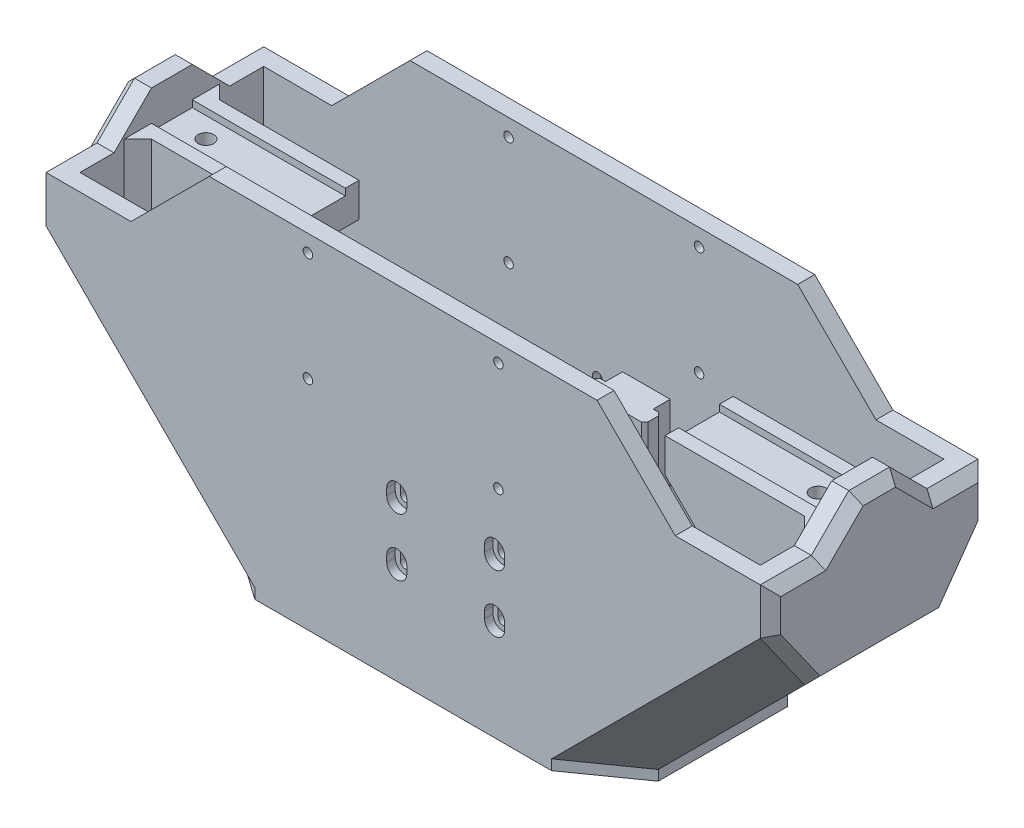
SolidWorks part; units mm, degrees
ref_plane "Front Plane" through (0, 0, 0) normal (0, 0, 1) x (1, 0, 0)
ref_plane "Top Plane" through (0, 0, 0) normal (0, 1, 0) x (1, 0, 0)
ref_plane "Right Plane" through (0, 0, 0) normal (1, 0, 0) x (0, 0, -1)
sketch "Sketch1" plane through (0, 0, 0) normal (0, 1, 0) x (1, 0, 0)
  line L1 (-100, -27) -> (100, -27)
  line L2 (-100, -27) -> (-100, 27)
  line L3 (-100, 27) -> (100, 27)
  line L4 (100, -27) -> (100, 27)
  line L5 (-100, -27) -> (100, 27) construction
  line L6 (-100, 27) -> (100, -27) construction
  point P0 (0, 0)
  dimension "D1" = 200
  dimension "D2" = 54
extrude "Boss-Extrude1" add sketch "Sketch1" along normal blind 70
shell "Shell1" thickness 5 removed face at (0, 70, 0) outward yes
sketch "Sketch2" plane through (105, 0, 0) normal (1, 0, 0) x (0, 0, -1)
  line L0 (-17, 70) -> (-6, 81)
  line L1 (-32, 70) -> (32, 70) construction
  line L2 (-6, 81) -> (6, 81)
  line L3 (6, 81) -> (17, 70)
  line L4 (17, 70) -> (-17, 70)
  line L5 (0, 81) -> (0, 75) construction
  dimension "D1" = 11
  dimension "D2" = 45
  dimension "D3" = 45
  dimension "D4" = 12
extrude "Boss-Extrude2" add sketch "Sketch2" against normal blind 5
sketch "Sketch4" plane through (0, 0, -32) normal (0, 0, -1) x (-1, 0, 0)
  line L0 (-80, 70) -> (-57, 93)
  line L1 (-105, 70) -> (105, 70) construction
  line L2 (-57, 93) -> (57, 93)
  line L3 (57, 93) -> (80, 70)
  line L4 (80, 70) -> (-80, 70)
  line L5 (0, 93) -> (0, 70) construction
  line L6 (-105, 70) -> (-105, -5) construction
  dimension "D1" = 23
  dimension "D2" = 25
  dimension "D3" = 45
extrude "Boss-Extrude3" add sketch "Sketch4" against normal blind 5
sketch "Sketch3" plane through (0, 0, -32) normal (0, 0, -1) x (-1, 0, 0)
  line L1 (-28, 56) -> (28, 56) construction
  line L2 (-28, 56) -> (-28, 88) construction
  line L3 (-28, 88) -> (28, 88) construction
  line L4 (28, 56) -> (28, 88) construction
  line L5 (-28, 56) -> (28, 88) construction
  line L6 (-28, 88) -> (28, 56) construction
  line L7 (57, 93) -> (-57, 93) construction
  circle A0 centre (-28, 88) radius 1.4
  circle A1 centre (-28, 56) radius 1.4
  circle A2 centre (28, 88) radius 1.4
  circle A3 centre (28, 56) radius 1.4
  point P0 (0, 72)
  dimension "D1" = 2.8
  dimension "D2" = 56
  dimension "D3" = 32
  dimension "D4" = 5
extrude "Cut-Extrude1" cut sketch "Sketch3" against normal blind 6
mirror "Mirror4" about plane through (0, 0, 0) normal (0, 0, 1) of "Boss-Extrude3", "Cut-Extrude1"
mirror "Mirror5" about plane through (0, 0, 0) normal (1, 0, 0) of "Boss-Extrude2"
sketch "Sketch5" plane through (0, 0, 0) normal (0, 0, 1) x (1, 0, 0)
  line L0 (-100, 70) -> (-55, 70)
  line L1 (-55, 70) -> (-55, 62)
  line L2 (-55, 62) -> (-100, 17)
  line L4 (-100, 17) -> (-100, 70)
  line L5 (-100, 81) -> (-100, 70) construction
  line L6 (-105, 70) -> (-80, 70) construction
  dimension "D1" = 45
  dimension "D2" = 8
  dimension "D3" = 45
extrude "Boss-Extrude4" add sketch "Sketch5" along normal mid plane 20
sketch "Sketch9" plane through (0, 70, 0) normal (0, 1, 0) x (1, 0, 0)
  line L4 (-55, 10) -> (-100, 10)
  line L5 (-100, 10) -> (-100, -10)
  line L6 (-100, -10) -> (-55, -10)
  line L7 (-55, -10) -> (-55, 10)
  line L8 (-55, 10) -> (-100, 10)
  line L10 (-100, -10) -> (-55, -10)
  line L11 (-55, -10) -> (-55, 10)
  line L13 (-100, 10) -> (-100, -10)
  dimension "D1" = 0
extrude "Boss-Extrude6" add sketch "Sketch9" along normal blind 2
sketch "Sketch10" plane through (-100, 0, 0) normal (1, 0, 0) x (0, 0, -1)
  line L0 (-10, 72) -> (10, 72) construction
  line L1 (-6, 72) -> (6, 72)
  line L2 (-6, 72) -> (-6, 70)
  line L3 (-6, 70) -> (6, 70)
  line L4 (6, 72) -> (6, 70)
  line L5 (-6, 72) -> (6, 70) construction
  line L6 (-6, 70) -> (6, 72) construction
  point P0 (0, 71)
  dimension "D1" = 2
  dimension "D2" = 12
extrude "Cut-Extrude2" cut sketch "Sketch10" along normal up to next
sketch "Sketch11" plane through (0, 70, 0) normal (0, 1, 0) x (1, 0, 0)
  line L1 (-100, 6) -> (-100, -6) construction
  circle A0 centre (-90, 0) radius 2.3
  dimension "D1" = 4.6
  dimension "D2" = 10
extrude "Cut-Extrude3" cut sketch "Sketch11" against normal blind 6
mirror "Mirror24" about plane through (0, 0, 0) normal (1, 0, 0) of "Cut-Extrude2", "Boss-Extrude4", "Boss-Extrude6", "Cut-Extrude3"
chamfer "Chamfer3" distance 40 angle 45 2 edges at (100, 0, 0) (-100, 0, 0)
chamfer "Chamfer5" distance 43 angle 45 2 edges at (105, -5, 0) (-105, -5, 0)
chamfer "Chamfer11" distance 10 angle 45 4 edges at (80, 20, 27) (80, 20, -27) (-80, 20, -27) (-80, 20, 27)
chamfer "Chamfer12" distance 13 angle 45 4 edges at (83.5, 16.5, -32) (83.5, 16.5, 32) (-83.5, 16.5, -32) (-83.5, 16.5, 32)
chamfer "Chamfer13" distance 4 angle 45 4 edges at (-100, 56, 10) (-100, 56, -10) (100, 56, 10) (100, 56, -10)
sketch "Sketch16" plane through (105, 0, 0) normal (1, 0, 0) x (0, 0, -1)
  line L10 (-19, 38) -> (19, 38)
  line L11 (19, 38) -> (32, 56.3848)
  line L12 (32, 56.3848) -> (32, 70)
  line L13 (32, 70) -> (17, 70)
  line L14 (17, 70) -> (6, 81)
  line L15 (6, 81) -> (-6, 81)
  line L16 (-6, 81) -> (-17, 70)
  line L17 (-17, 70) -> (-32, 70)
  line L18 (-32, 70) -> (-32, 56.3848)
  line L19 (-32, 56.3848) -> (-19, 38)
  line L20 (-19, 38) -> (19, 38)
  line L21 (19, 38) -> (32, 56.3848)
  line L22 (32, 56.3848) -> (32, 70)
  line L23 (32, 70) -> (17, 70)
  line L24 (17, 70) -> (6, 81)
  line L25 (6, 81) -> (-6, 81)
  line L26 (-6, 81) -> (-17, 70)
  line L27 (-17, 70) -> (-32, 70)
  line L28 (-32, 70) -> (-32, 56.3848)
  line L29 (-32, 56.3848) -> (-19, 38)
  dimension "D1" = 0
extrude "Boss-Extrude10" add sketch "Sketch16" along normal blind 3
chamfer "Chamfer14" distance 3 angle 45 10 edges at (108, 63.1924, 32) (108, 70, 24.5) (108, 75.5, 11.5) (108, 81, 0) (108, 75.5, -11.5) (108, 70, -24.5) (108, 63.1924, -32) (108, 47.1924, -25.5) (108, 38, 0) (108, 47.1924, 25.5)
mirror "Mirror28" about plane through (0, 0, 0) normal (1, 0, 0) of "Chamfer14", "Boss-Extrude10"
sketch "Sketch17" plane through (0, 0, 0) normal (0, 1, 0) x (1, 0, 0)
  line L0 (-57, -27) -> (57, -27) construction
  line L1 (5.5, -27) -> (19.5, -27)
  line L2 (5.5, -27) -> (5.5, -22)
  line L3 (5.5, -22) -> (19.5, -22)
  line L4 (19.5, -27) -> (19.5, -22)
  line L5 (5.5, -27) -> (19.5, -22) construction
  line L6 (5.5, -22) -> (19.5, -27) construction
  line L7 (3, -22) -> (22, -22)
  line L8 (3, -22) -> (3, -17)
  line L9 (3, -17) -> (22, -17)
  line L10 (22, -22) -> (22, -17)
  line L11 (3, -22) -> (22, -17) construction
  line L12 (3, -17) -> (22, -22) construction
  point P0 (12.5, -24.5)
  point P5 (12.5, -19.5)
  line M10 (-45.8579, -27) -> (45.8579, -27)
  dimension "D1" = 19
  dimension "D2" = 14
  dimension "D3" = 5
  dimension "D4" = 12.5
extrude "Boss-Extrude11" add sketch "Sketch17" along normal blind 45 contours L7 L10 L9 L8 L3 | L4 L3 L2 M10 region at (12.5, 0, 24.5) region at (12.5, 0, 19.5)
sketch "Sketch20" plane through (0, 0, 0) normal (0, 1, 0) x (1, 0, 0)
  line L0 (22, -22) -> (22, -17) construction
  line L1 (3, -17) -> (22, -17)
  line L2 (3, -17) -> (3, -12)
  line L3 (3, -12) -> (22, -12)
  line L4 (22, -17) -> (22, -12)
  dimension "D1" = 5
extrude "Boss-Extrude14" add sketch "Sketch20" along normal blind 8
mirror "Mirror29" about plane through (0, 0, 0) normal (0, 0, 1) of "Boss-Extrude14", "Boss-Extrude11"
sketch "Sketch22" plane through (0, 0, -27) normal (0, 0, 1) x (1, 0, 0)
  line L0 (5.5, 0) -> (-45.8579, 0) construction
  line L1 (-1.875, 21.8) -> (26.875, 21.8) construction
  line L2 (-1.875, 21.8) -> (-1.875, 38.8) construction
  line L3 (-1.875, 38.8) -> (26.875, 38.8) construction
  line L4 (26.875, 21.8) -> (26.875, 38.8) construction
  line L5 (-1.875, 21.8) -> (26.875, 38.8) construction
  line L6 (-1.875, 38.8) -> (26.875, 21.8) construction
  line L7 (3, 45) -> (22, 45) construction
  line L8 (-1.875, 37.8) -> (-1.875, 39.8) construction
  line L9 (-3.325, 37.8) -> (-3.325, 39.8)
  line L10 (-0.425, 37.8) -> (-0.425, 39.8)
  line L11 (12.5, 38.8) -> (12.5, 30.3) construction
  line L12 (12.5, 30.3) -> (-1.875, 30.3) construction
  line L13 (26.875, 37.8) -> (26.875, 39.8) construction
  line L14 (28.325, 37.8) -> (28.325, 39.8)
  line L15 (25.425, 37.8) -> (25.425, 39.8)
  line L16 (-1.875, 22.8) -> (-1.875, 20.8) construction
  line L17 (-3.325, 22.8) -> (-3.325, 20.8)
  line L18 (-0.425, 22.8) -> (-0.425, 20.8)
  line L19 (26.875, 22.8) -> (26.875, 20.8) construction
  line L20 (28.325, 22.8) -> (28.325, 20.8)
  line L21 (25.425, 22.8) -> (25.425, 20.8)
  arc A4 (-3.325, 37.8) -> (-0.425, 37.8) centre (-1.875, 37.8) ccw
  arc A5 (-0.425, 39.8) -> (-3.325, 39.8) centre (-1.875, 39.8) ccw
  arc A6 (28.325, 37.8) -> (25.425, 37.8) centre (26.875, 37.8) cw
  arc A7 (25.425, 39.8) -> (28.325, 39.8) centre (26.875, 39.8) cw
  arc A8 (-3.325, 22.8) -> (-0.425, 22.8) centre (-1.875, 22.8) cw
  arc A9 (-0.425, 20.8) -> (-3.325, 20.8) centre (-1.875, 20.8) cw
  arc A10 (28.325, 22.8) -> (25.425, 22.8) centre (26.875, 22.8) ccw
  arc A11 (25.425, 20.8) -> (28.325, 20.8) centre (26.875, 20.8) ccw
  point P0 (12.5, 30.3)
  point P7 (12.5, 45)
  point P11 (-1.875, 38.8)
  point P22 (26.875, 38.8)
  point P29 (-1.875, 21.8)
  point P36 (26.875, 21.8)
  dimension "D4" = 1.45
  dimension "D1" = 21.8
  dimension "D2" = 28.75
  dimension "D3" = 17
  dimension "D5" = 2
extrude "Cut-Extrude4" cut sketch "Sketch22" against normal blind 2.5
sketch "Sketch23" plane through (0, 0, -29.5) normal (0, 0, 1) x (1, 0, 0)
  line L6 (29.825, 37.8) -> (29.825, 39.8)
  line L7 (23.925, 39.8) -> (23.925, 37.8)
  line L8 (29.825, 37.8) -> (29.825, 39.8)
  line L9 (23.925, 39.8) -> (23.925, 37.8)
  line L12 (1.075, 37.8) -> (1.075, 39.8)
  line L13 (-4.825, 39.8) -> (-4.825, 37.8)
  line L14 (1.075, 37.8) -> (1.075, 39.8)
  line L15 (-4.825, 39.8) -> (-4.825, 37.8)
  line L18 (-4.825, 22.8) -> (-4.825, 20.8)
  line L19 (1.075, 20.8) -> (1.075, 22.8)
  line L20 (-4.825, 22.8) -> (-4.825, 20.8)
  line L21 (1.075, 20.8) -> (1.075, 22.8)
  line L24 (23.925, 22.8) -> (23.925, 20.8)
  line L25 (29.825, 20.8) -> (29.825, 22.8)
  line L26 (23.925, 22.8) -> (23.925, 20.8)
  line L27 (29.825, 20.8) -> (29.825, 22.8)
  arc A6 (23.925, 37.8) -> (29.825, 37.8) centre (26.875, 37.8) ccw
  arc A7 (29.825, 39.8) -> (23.925, 39.8) centre (26.875, 39.8) ccw
  arc A8 (23.925, 37.8) -> (29.825, 37.8) centre (26.875, 37.8) ccw
  arc A9 (29.825, 39.8) -> (23.925, 39.8) centre (26.875, 39.8) ccw
  arc A12 (-4.825, 37.8) -> (1.075, 37.8) centre (-1.875, 37.8) ccw
  arc A13 (1.075, 39.8) -> (-4.825, 39.8) centre (-1.875, 39.8) ccw
  arc A14 (-4.825, 37.8) -> (1.075, 37.8) centre (-1.875, 37.8) ccw
  arc A15 (1.075, 39.8) -> (-4.825, 39.8) centre (-1.875, 39.8) ccw
  arc A18 (1.075, 22.8) -> (-4.825, 22.8) centre (-1.875, 22.8) ccw
  arc A19 (-4.825, 20.8) -> (1.075, 20.8) centre (-1.875, 20.8) ccw
  arc A20 (1.075, 22.8) -> (-4.825, 22.8) centre (-1.875, 22.8) ccw
  arc A21 (-4.825, 20.8) -> (1.075, 20.8) centre (-1.875, 20.8) ccw
  arc A24 (29.825, 22.8) -> (23.925, 22.8) centre (26.875, 22.8) ccw
  arc A25 (23.925, 20.8) -> (29.825, 20.8) centre (26.875, 20.8) ccw
  arc A26 (29.825, 22.8) -> (23.925, 22.8) centre (26.875, 22.8) ccw
  arc A27 (23.925, 20.8) -> (29.825, 20.8) centre (26.875, 20.8) ccw
  dimension "D1" = 1.5
  dimension "D2" = 1.5
  dimension "D3" = 1.5
  dimension "D4" = 1.5
extrude "Cut-Extrude5" cut sketch "Sketch23" against normal up to next contours A8 L8 A9 L9 | A14 L14 A15 L15 | A20 L20 A21 L21 | A26 L26 A27 L27
mirror "Mirror30" about plane through (0, 0, 0) normal (0, 0, 1) of "Cut-Extrude5", "Cut-Extrude4"
sketch "Sketch24" plane through (30, -30, 0) normal (-0.7071, 0.7071, 0) x (0, 0, 1)
  line L0 (17, 42.4264) -> (-17, 42.4264) construction
  line L1 (-7.5, 47.4264) -> (7.5, 47.4264)
  line L2 (-7.5, 47.4264) -> (-7.5, 55.4264)
  line L3 (-7.5, 55.4264) -> (7.5, 55.4264)
  line L4 (7.5, 47.4264) -> (7.5, 55.4264)
  line L5 (-7.5, 47.4264) -> (7.5, 55.4264) construction
  line L6 (-7.5, 55.4264) -> (7.5, 47.4264) construction
  point P0 (0, 51.4264)
  dimension "D1" = 5
  dimension "D2" = 15
  dimension "D3" = 8
extrude "Cut-Extrude6" cut sketch "Sketch24" against normal up to next
chamfer "Chamfer18" distance 4 angle 45 4 edges at (22, 0, 17) (22, 0, -17) (3, 0, 17) (3, 0, -17)
chamfer "Chamfer19" distance 1 angle 45 8 edges at (3, 24.5, 22) (22, 26.5, 17) (22, 24.5, 22) (3, 26.5, 17) (22, 24.5, -22) (22, 26.5, -17) (3, 26.5, -17) (3, 24.5, -22)
chamfer "Chamfer20" distance 2 angle 45 4 edges at (65.2855, 1.7855, -7.5) (65.2855, 1.7855, 7.5) (70.9424, 7.4424, 7.5) (70.9424, 7.4424, -7.5)
sketch "Sketch25" plane through (0, -5, 0) normal (0, -1, 0) x (1, 0, 0)
  line L8 (-43.6152, -32) -> (43.6152, -32)
  line L9 (43.6152, -32) -> (62, -19)
  line L10 (62, -19) -> (62, 19)
  line L11 (62, 19) -> (43.6152, 32)
  line L12 (43.6152, 32) -> (-43.6152, 32)
  line L13 (-43.6152, 32) -> (-62, 19)
  line L14 (-62, 19) -> (-62, -19)
  line L15 (-62, -19) -> (-43.6152, -32)
  line L16 (-43.6152, -32) -> (43.6152, -32)
  line L17 (43.6152, -32) -> (62, -19)
  line L18 (62, -19) -> (62, 19)
  line L19 (62, 19) -> (43.6152, 32)
  line L20 (43.6152, 32) -> (-43.6152, 32)
  line L21 (-43.6152, 32) -> (-62, 19)
  line L22 (-62, 19) -> (-62, -19)
  line L23 (-62, -19) -> (-43.6152, -32)
  dimension "D1" = 0
extrude "Boss-Extrude15" add sketch "Sketch25" along normal blind 3
sketch "Sketch27" plane through (0, 0, 0) normal (0, 1, 0) x (1, 0, 0)
  line L0 (26, 12) -> (-1, 12) construction
  line L1 (-30, -12) -> (30, -12)
  line L2 (-30, -12) -> (-30, 12)
  line L3 (-30, 12) -> (30, 12)
  line L4 (30, -12) -> (30, 12)
  line L5 (22, -12) -> (3, -12) construction
  line L6 (-30, 12) -> (30, -12) construction
  point P8 (0, 0)
  point P9 (0, 0)
  dimension "D1" = 60
extrude "Cut-Extrude7" cut sketch "Sketch27" against normal up to next
chamfer "Chamfer21" distance 5 angle 45 4 edges at (-30, -4, -12) (30, -4, -12) (30, -4, 12) (-30, -4, 12)
sketch "Sketch28" plane through (0, -8, 0) normal (0, -1, 0) x (1, 0, 0)
  line L0 (62, 19) -> (43.6152, 32) construction
  line L1 (-52.8076, -25.5) -> (52.8076, -25.5) construction
  line L2 (-52.8076, -25.5) -> (-52.8076, 25.5) construction
  line L3 (-52.8076, 25.5) -> (52.8076, 25.5) construction
  line L4 (52.8076, -25.5) -> (52.8076, 25.5) construction
  line L5 (-52.8076, -25.5) -> (52.8076, 25.5) construction
  line L6 (-52.8076, 25.5) -> (52.8076, -25.5) construction
  circle A0 centre (-52.8076, 0) radius 2.75
  circle A1 centre (-52.8076, 15) radius 2.75
  circle A2 centre (-52.8076, -15) radius 2.75
  point P0 (0, 0)
  point P15 (-52.8076, -11.7106)
  dimension "D1" = 5.5
  dimension "D2" = 15
  dimension "D3" = 15
extrude "Cut-Extrude8" cut sketch "Sketch28" against normal blind 6
mirror "Mirror31" about plane through (0, 0, 0) normal (1, 0, 0) of "Cut-Extrude8"
sketch "Sketch29" plane through (0, -8, 0) normal (0, -1, 0) x (1, 0, 0)
  line L0 (-54.9289, 24) -> (54.9289, 24) construction
  line L3 (43.6152, 32) -> (-43.6152, 32) construction
  line L4 (-43.6152, 32) -> (-62, 19) construction
  line L5 (62, 19) -> (43.6152, 32) construction
  circle A1 centre (0, 24) radius 2.75
  circle A2 centre (20, 24) radius 2.75
  circle A3 centre (40, 24) radius 2.75
  point P4 (-54.9289, 24)
  point P9 (54.9289, 24)
  dimension "D1" = 5.5
  dimension "D3" = 20
  dimension "D4" = 8
  dimension "D2" = 3
extrude "Cut-Extrude9" cut sketch "Sketch29" against normal blind 6
mirror "Mirror32" about plane through (0, 0, 0) normal (1, 0, 0) of "Cut-Extrude9"
mirror "Mirror33" about plane through (0, 0, 0) normal (0, 0, 1) of "Mirror32"
sketch "Sketch32" plane through (0, -2, 0) normal (0, -1, 0) x (1, 0, 0)
  circle A0 centre (-40, 24) radius 1.9
  circle A1 centre (-52.8076, 15) radius 1.9
  circle A2 centre (-52.8076, 0) radius 1.9
  dimension "D1" = 3.8
extrude "Cut-Extrude11" cut sketch "Sketch32" against normal blind 2
mirror "Mirror34" about plane through (0, 0, 0) normal (0, 0, 1) of "Cut-Extrude11"
mirror "Mirror35" about plane through (0, 0, 0) normal (1, 0, 0) of "Mirror34"
